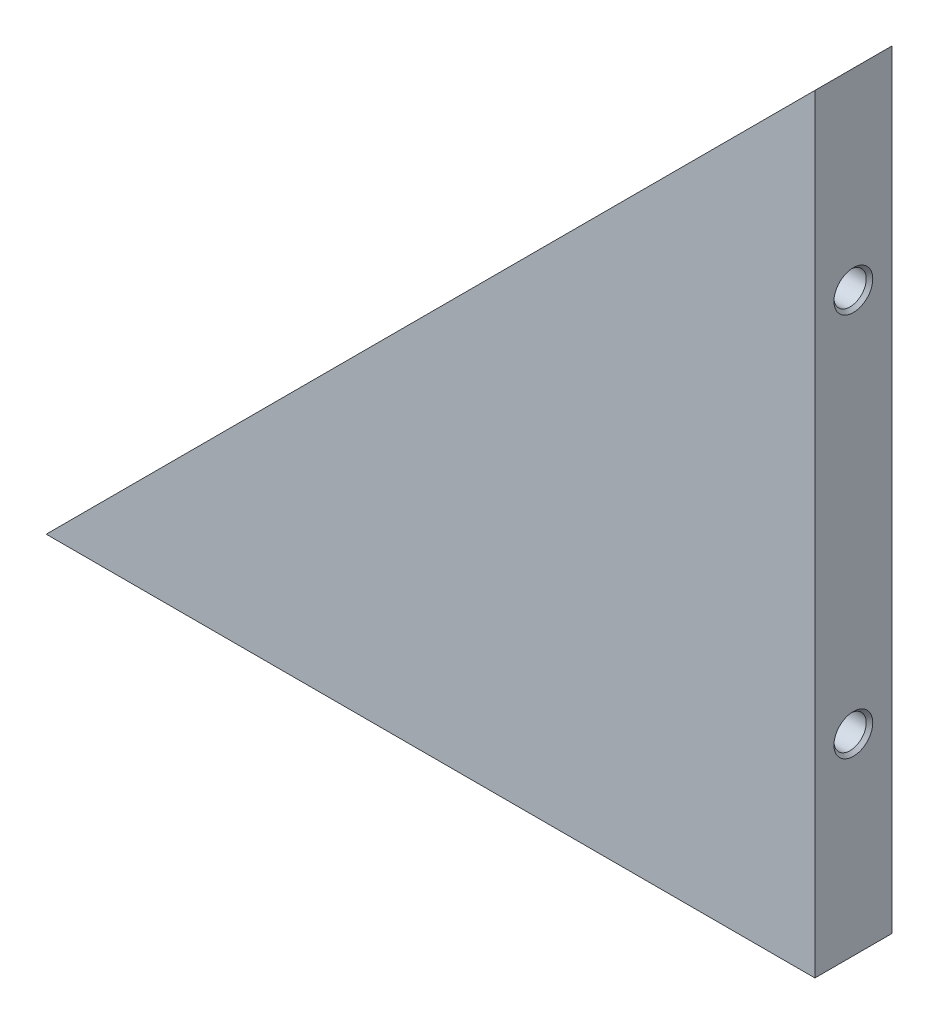
SolidWorks part; units mm, degrees
ref_plane "Vorne" through (0, 0, 0) normal (0, 0, 1) x (1, 0, 0)
ref_plane "Oben" through (0, 0, 0) normal (0, 1, 0) x (1, 0, 0)
ref_plane "Rechts" through (0, 0, 0) normal (1, 0, 0) x (0, 0, -1)
ref_plane "E_Boden" through (0, 1, 0) normal (0, 1, 0) x (1, 0, 0)
sketch "Skizze1" plane through (0, 0, 0) normal (0, 0, 1) x (1, 0, 0)
  line L0 (0, 10) -> (0, -9.5229) construction
  line L1 (-15.5467, 0) -> (14.4334, 0) construction
  line L2 (100, 0) -> (100, 100)
  line L3 (100, 100) -> (0, 0)
  line L4 (0, 0) -> (100, 0)
  dimension "D1" = 100
  dimension "D2" = 100
extrude "Aufsatz-Linear austragen1" add sketch "Skizze1" along normal blind 10
hole_wizard "M5 Gewindebohrung2" positions "Skizze7" profile "Skizze8" tap size "M5" standard "DIN"
sketch "Skizze7" plane through (100, 0, 0) normal (1, 0, 0) x (0, 0, -1)
  line L2 (-5, 100) -> (-5, 0) construction
  line L3 (-10, 100) -> (0, 100) construction
  line L4 (-10, 0) -> (0, 0) construction
  line L6 (-10, 50) -> (0, 50) construction
  line L7 (-10, 0) -> (-10, 100) construction
  line L8 (0, 0) -> (0, 100) construction
  point P0 (-5, 75)
  point P2 (-5, 25)
  dimension "D1" = 50
sketch "Skizze8" plane through (100, 75, 5) normal (0, 1, 0) x (0, 0, -1)
  line L0 (0, 0) -> (0, 21.2618)
  line L1 (0, 21.2618) -> (2.1, 20)
  line L2 (2.1, 20) -> (2.1, 0.425)
  line L3 (2.1, 0.425) -> (2.525, 0)
  line L5 (2.525, 0) -> (0, 0)
  line L6 (-2.1, 0.425) -> (-2.525, 0) construction
  line L10 (0, 21.2618) -> (-2.1, 20) construction
  line L11 (0, -6.35) -> (0, 107.95) construction
  dimension "Bohrerdurchmesser" = 4.2
  dimension "Bohrungstiefe" = 20
  dimension "Senkdurchmesser (Oben)" = 5.05
  dimension "Senkwinkel (Oben)" = 90
  dimension "Spitzenwinkel" = 118
cosmetic thread "Bohrungsgewinde3" parameters "D1"=10, "D2"=5
cosmetic thread "Bohrungsgewinde4" parameters "D1"=10, "D2"=5
hole_wizard "M5 Gewindebohrung3" positions "Skizze9" profile "Skizze10" tap size "M5" standard "DIN"
sketch "Skizze9" plane through (0, 0, 0) normal (0, -1, 0) x (-1, 0, 0)
  line L0 (-100, -5) -> (0, -5) construction
  line L1 (-100, -10) -> (-100, 0) construction
  line L2 (0, -10) -> (0, 0) construction
  line L4 (-50, 0) -> (-50, -10) construction
  line L5 (0, 0) -> (-100, 0) construction
  line L6 (0, -10) -> (-100, -10) construction
  point P0 (-25, -5)
  point P2 (-75, -5)
  dimension "D1" = 50
sketch "Skizze10" plane through (25, 0, 5) normal (1, 0, 0) x (0, 0, -1)
  line L0 (0, 0) -> (0, 21.2618)
  line L1 (0, 21.2618) -> (2.1, 20)
  line L2 (2.1, 20) -> (2.1, 0.425)
  line L3 (2.1, 0.425) -> (2.525, 0)
  line L5 (2.525, 0) -> (0, 0)
  line L6 (-2.1, 0.425) -> (-2.525, 0) construction
  line L10 (0, 21.2618) -> (-2.1, 20) construction
  line L11 (0, -6.35) -> (0, 107.95) construction
  dimension "Bohrerdurchmesser" = 4.2
  dimension "Bohrungstiefe" = 20
  dimension "Senkdurchmesser (Oben)" = 5.05
  dimension "Senkwinkel (Oben)" = 90
  dimension "Spitzenwinkel" = 118
cosmetic thread "Bohrungsgewinde5" parameters "D1"=10, "D2"=5
cosmetic thread "Bohrungsgewinde6" parameters "D1"=10, "D2"=5
